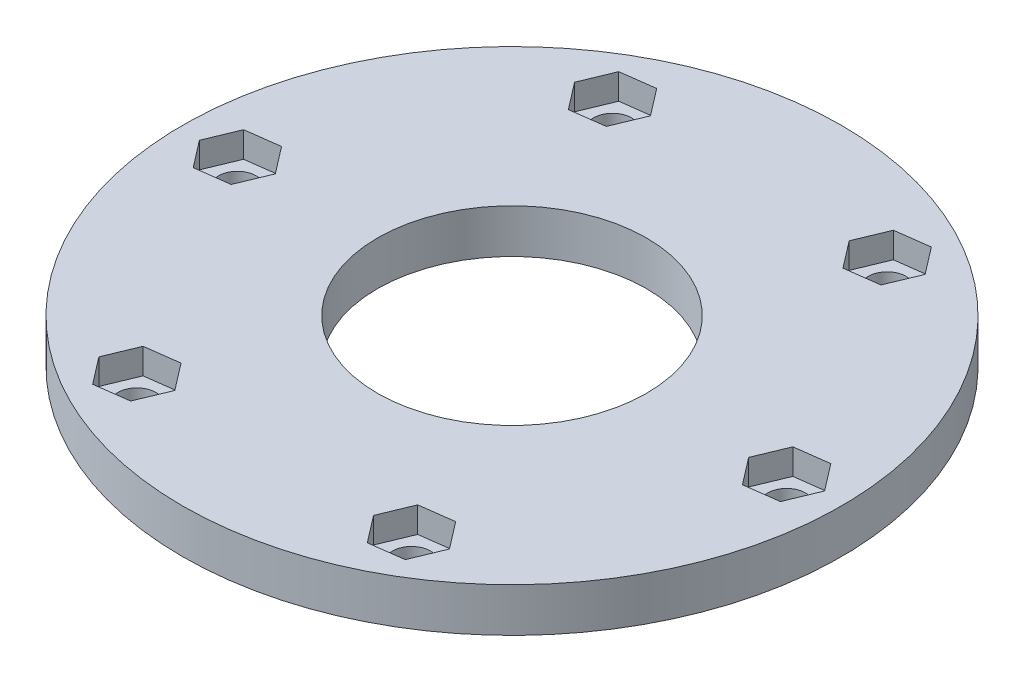
SolidWorks part; units mm, degrees
ref_plane "Front Plane" through (0, 0, 0) normal (0, 0, 1) x (1, 0, 0)
ref_plane "Top Plane" through (0, 0, 0) normal (0, 1, 0) x (1, 0, 0)
ref_plane "Right Plane" through (0, 0, 0) normal (1, 0, 0) x (0, 0, -1)
sketch "Sketch2" plane through (0, 0, 0) normal (0, 1, 0) x (1, 0, 0)
  line L0 (22.1383, 27.5775) -> (23.9031, 31.8459)
  line L1 (-15.3617, 27.5775) -> (-13.5969, 31.8459)
  line L2 (-13.5969, 31.8459) -> (-16.4111, 35.5084)
  line L3 (-16.4111, 35.5084) -> (-20.99, 34.9025)
  line L4 (-20.99, 34.9025) -> (-22.7547, 30.6341)
  line L5 (-22.7547, 30.6341) -> (-19.9406, 26.9716)
  line L6 (-19.9406, 26.9716) -> (-15.3617, 27.5775)
  line L7 (23.9031, 31.8459) -> (21.0889, 35.5084)
  line L8 (21.0889, 35.5084) -> (16.51, 34.9025)
  line L9 (14.7453, 30.6341) -> (17.5594, 26.9716)
  line L10 (16.51, 34.9025) -> (14.7453, 30.6341)
  line L11 (17.5594, 26.9716) -> (22.1383, 27.5775)
  line L12 (36.3094, -5.5043) -> (40.8883, -4.8984)
  line L13 (40.8883, -4.8984) -> (42.6531, -0.6301)
  line L14 (42.6531, -0.6301) -> (39.8389, 3.0324)
  line L15 (35.26, 2.4266) -> (33.4953, -1.8418)
  line L16 (39.8389, 3.0324) -> (35.26, 2.4266)
  line L17 (33.4953, -1.8418) -> (36.3094, -5.5043)
  line L18 (14.7453, -34.3178) -> (17.5594, -37.9803)
  line L19 (17.5594, -37.9803) -> (22.1383, -37.3744)
  line L20 (22.1383, -37.3744) -> (23.9031, -33.106)
  line L21 (21.0889, -29.4435) -> (16.51, -30.0494)
  line L22 (23.9031, -33.106) -> (21.0889, -29.4435)
  line L23 (16.51, -30.0494) -> (14.7453, -34.3178)
  line L24 (-20.99, -30.0494) -> (-22.7547, -34.3178)
  line L25 (-22.7547, -34.3178) -> (-19.9406, -37.9803)
  line L26 (-19.9406, -37.9803) -> (-15.3617, -37.3744)
  line L27 (-13.5969, -33.106) -> (-16.4111, -29.4435)
  line L28 (-15.3617, -37.3744) -> (-13.5969, -33.106)
  line L29 (-16.4111, -29.4435) -> (-20.99, -30.0494)
  line L30 (-35.1611, 3.0324) -> (-39.74, 2.4266)
  line L31 (-39.74, 2.4266) -> (-41.5047, -1.8418)
  line L32 (-41.5047, -1.8418) -> (-38.6906, -5.5043)
  line L33 (-34.1117, -4.8984) -> (-32.3469, -0.6301)
  line L34 (-38.6906, -5.5043) -> (-34.1117, -4.8984)
  line L35 (-32.3469, -0.6301) -> (-35.1611, 3.0324)
  circle A30 centre (-36.9258, -1.2359) radius 4
  circle A31 centre (-18.1758, 31.24) radius 4.575
  circle A32 centre (19.3242, 31.24) radius 4
  circle A33 centre (38.0742, -1.2359) radius 4
  circle A34 centre (19.3242, -33.7119) radius 4
  circle A35 centre (-18.1758, -33.7119) radius 4
  circle A36 centre (0.5742, -1.2359) radius 45
  circle A37 centre (0.5742, -1.2359) radius 18.375
  circle A38 centre (-18.1758, 31.24) radius 4 construction
  circle A39 centre (-18.1758, 31.24) radius 2.575
  circle A40 centre (19.3242, 31.24) radius 2.575
  circle A41 centre (38.0742, -1.2359) radius 2.575
  circle A42 centre (19.3242, -33.7119) radius 2.575
  circle A43 centre (-18.1758, -33.7119) radius 2.575
  circle A44 centre (-36.9258, -1.2359) radius 2.575
  dimension "D2" = 6
  dimension "D3" = 8
  dimension "D4" = 9.15
  dimension "D5" = 8
  dimension "D6" = 8
  dimension "D7" = 90
  dimension "D8" = 36.75
  dimension "D9" = 8
  dimension "D10" = 8
  dimension "D11" = 5.15
  dimension "D1" = 8
  dimension "D12" = 6
extrude "Boss-Extrude1" add sketch "Sketch2" along normal blind 6 contours A36 | A37
extrude "Cut-Extrude1" cut sketch "Sketch2<3>" along normal through all contours A40 | A39 | A42 | A41 | A43 | A44
sketch "Sketch2<3>" plane through (0, 0, 0) normal (0, 1, 0) x (1, 0, 0) same geometry as "Sketch2"
extrude "Cut-Extrude3" cut sketch "Sketch2<5>" against normal blind 3.5 from surface contours L3 L4 L5 L6 L1 L2 | L10 L9 L11 L0 L7 L8 | L16 L15 L17 L12 L13 L14 | L19 L20 L22 L21 L23 L18 | L30 L31 L32 L34 L33 L35 | L26 L28 L27 L29 L24 L25 starting at face at (-36.9258, 6, 3.8109)
sketch "Sketch2<5>" plane through (0, 0, 0) normal (0, 1, 0) x (1, 0, 0) same geometry as "Sketch2"
equation "\"R\"= 63mm"
equation "\"E\"= 2mm"
equation "\"Rr\"= 5"
equation "\"N\"= 22"
equation "\"M5\"= 5"
equation "\"SMALL_BEARING_DEPTH\"= 6MM"
